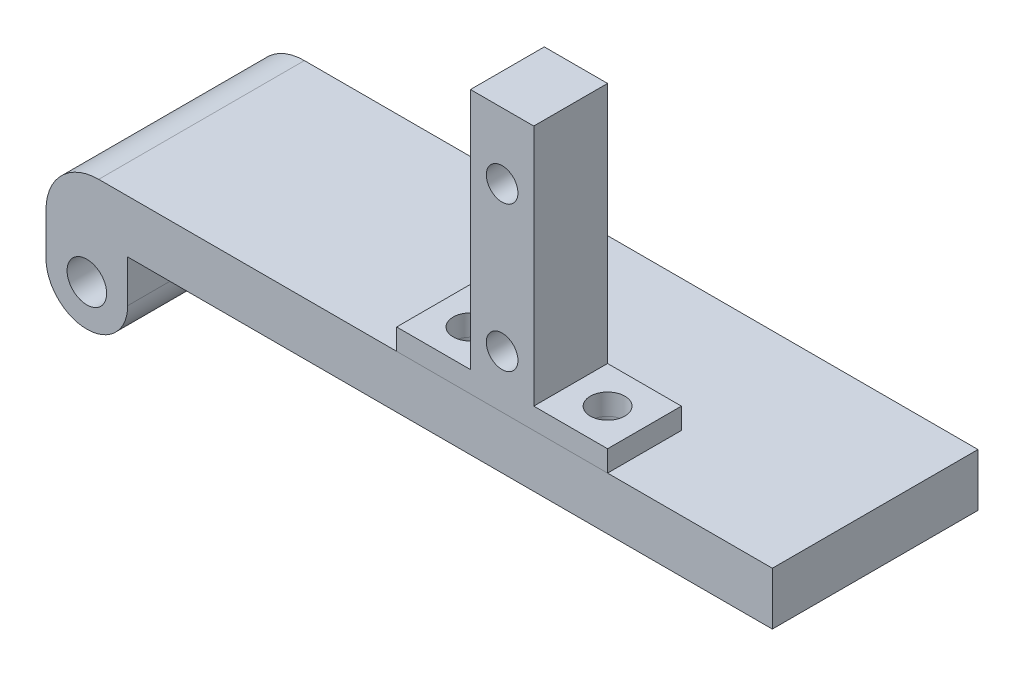
SolidWorks part; units mm, degrees
other "Motor Mount"
other "Lever Arm"
ref_plane "Front Plane" through (0, 0, 0) normal (0, 0, 1) x (1, 0, 0)
ref_plane "Top Plane" through (0, 0, 0) normal (0, 1, 0) x (1, 0, 0)
ref_plane "Right Plane" through (0, 0, 0) normal (1, 0, 0) x (0, 0, -1)
sketch "Sketch1" plane through (0, 0, 0) normal (0, 0, 1) x (1, 0, 0)
  line L0 (-37.3856, -8.255) -> (-37.3856, -3.175)
  line L1 (-37.3856, 3.175) -> (37.3856, 3.175)
  line L2 (-37.3856, 3.175) -> (-37.3856, -3.175)
  line L3 (-27.5431, -3.175) -> (37.3856, -3.175)
  line L4 (37.3856, 3.175) -> (37.3856, -3.175)
  line L5 (-37.3856, 3.175) -> (37.3856, -3.175) construction
  line L6 (-37.3856, -3.175) -> (37.3856, 3.175) construction
  line L7 (-27.5431, -8.255) -> (-27.5431, -3.175)
  circle A0 centre (-32.4644, -8.255) radius 2.3812
  arc A1 (-37.3856, -8.255) -> (-27.5431, -8.255) centre (-32.4644, -8.255) ccw
  point P0 (0, 0)
  dimension "D1" = 4.7625
  dimension "D3" = 2.54
  dimension "D2" = 6.35
  dimension "D4" = 69.85
  dimension "D5" = 5.08
extrude "Boss-Extrude1" add sketch "Sketch1" along normal blind 38.1
fillet "Fillet1" radius 6.35 1 edges at (-37.3856, 3.175, 19.05)
sketch "Sketch3" plane through (37.3856, 0, 0) normal (1, 0, 0) x (0, 0, -1)
  line L4 (0, -3.175) -> (0, 3.175)
  line L5 (0, 3.175) -> (-38.1, 3.175)
  line L6 (-38.1, 3.175) -> (-38.1, -3.175)
  line L7 (-38.1, -3.175) -> (0, -3.175)
  line L8 (0, -3.175) -> (0, 3.175)
  line L9 (0, 3.175) -> (-38.1, 3.175)
  line L10 (-38.1, 3.175) -> (-38.1, -3.175)
  line L11 (-38.1, -3.175) -> (0, -3.175)
  dimension "D1" = 0
extrude "Boss-Extrude2" add sketch "Sketch3" along normal blind 12.7
sketch "Sketch2" plane through (0, 3.175, 0) normal (0, 1, 0) x (1, 0, 0)
  line L1 (48.4981, -15.875) -> (11.9856, -15.875) construction
  line L2 (48.4981, -15.875) -> (48.4981, 0) construction
  line L3 (48.4981, 0) -> (11.9856, 0) construction
  line L4 (11.9856, -15.875) -> (11.9856, 0) construction
  line L5 (48.4981, -15.875) -> (11.9856, 0) construction
  line L6 (48.4981, 0) -> (11.9856, -15.875) construction
  line L7 (11.9856, -17.4625) -> (-16.5894, -17.4625) construction
  line L8 (11.9856, -17.4625) -> (11.9856, 1.5875) construction
  line L9 (11.9856, 1.5875) -> (-16.5894, 1.5875) construction
  line L10 (-16.5894, -17.4625) -> (-16.5894, 1.5875) construction
  line L11 (11.9856, -17.4625) -> (-16.5894, 1.5875) construction
  line L12 (11.9856, 1.5875) -> (-16.5894, -17.4625) construction
  line L13 (37.3856, -25.4) -> (37.3856, 9.525) construction
  line L14 (50.0856, 0) -> (-31.0356, 0) construction
  line L15 (-34.8456, -38.1) -> (-30.0831, -38.1) construction
  line L16 (-34.8456, -38.1) -> (-30.0831, -38.1) construction
  line L18 (21.3519, -24.765) -> (13.7319, -24.765)
  line L19 (21.3519, -24.765) -> (21.3519, -15.875)
  line L20 (21.3519, -15.875) -> (13.7319, -15.875)
  line L21 (13.7319, -24.765) -> (13.7319, -15.875)
  line L22 (21.3519, -24.765) -> (13.7319, -15.875) construction
  line L23 (21.3519, -15.875) -> (13.7319, -24.765) construction
  point P0 (30.2419, -7.9375)
  point P5 (17.5419, -20.32)
  point P6 (-2.3019, -7.9375)
  point P15 (17.5419, -20.32)
  point P21 (-32.4644, -38.1)
  point P26 (37.3856, -7.9375)
  dimension "Motor_Pos" = 15.875
  dimension "D2" = 36.5125
  dimension "D3" = 28.575
  dimension "D4" = 19.05
  dimension "D5" = 5.5562
  dimension "D6" = 11.1125
  dimension "D7" = 34.925
  dimension "D8" = 69.85
  dimension "D9" = 8.89
  dimension "D10" = 7.62
extrude "Boss-Extrude3" add sketch "Sketch2" along normal blind 31.75
sketch "Sketch5" plane through (0, 0, 24.765) normal (0, 0, 1) x (1, 0, 0)
  line L0 (17.5419, 34.925) -> (17.5419, 3.175) construction
  line L1 (13.7319, 34.925) -> (21.3519, 34.925) construction
  line L2 (13.7319, 3.175) -> (21.3519, 3.175) construction
  circle A0 centre (17.5419, 9.525) radius 1.905
  circle A1 centre (17.5419, 26.9875) radius 1.905
  dimension "D1" = 3.81
  dimension "D2" = 17.4625
  dimension "D3" = 6.35
extrude "Cut-Extrude1" cut sketch "Sketch5" against normal through all both and the other way through all
sketch "Sketch6" plane through (0, 3.175, 0) normal (0, 1, 0) x (1, 0, 0)
  line L0 (13.7319, -24.765) -> (21.3519, -24.765) construction
  line L1 (30.2419, -24.765) -> (4.8419, -24.765)
  line L2 (30.2419, -24.765) -> (30.2419, -15.875)
  line L3 (30.2419, -15.875) -> (4.8419, -15.875)
  line L4 (4.8419, -24.765) -> (4.8419, -15.875)
  line L5 (30.2419, -24.765) -> (4.8419, -15.875) construction
  line L6 (30.2419, -15.875) -> (4.8419, -24.765) construction
  line L7 (21.3519, -15.875) -> (13.7319, -15.875) construction
  line L8 (15.6369, -24.765) -> (19.4469, -24.765) construction
  line L9 (15.6369, -24.765) -> (19.4469, -24.765) construction
  line L10 (13.7319, -15.875) -> (13.7319, -24.765) construction
  point P0 (17.5419, -20.32)
  point P14 (17.5419, -24.765)
  dimension "D1" = 25.4
  dimension "D2" = 8.89
  dimension "D3" = 8.89
extrude "Boss-Extrude4" add sketch "Sketch6" along normal blind 2.54
sketch "Sketch7" plane through (0, 5.715, 0) normal (0, 1, 0) x (1, 0, 0)
  line L0 (4.8419, -24.765) -> (30.2419, -24.765) construction
  line L1 (13.7319, -24.765) -> (4.8419, -24.765) construction
  line L2 (13.7319, -24.765) -> (13.7319, -15.875) construction
  line L3 (13.7319, -15.875) -> (4.8419, -15.875) construction
  line L4 (4.8419, -24.765) -> (4.8419, -15.875) construction
  line L5 (13.7319, -24.765) -> (4.8419, -15.875) construction
  line L6 (13.7319, -15.875) -> (4.8419, -24.765) construction
  line L7 (13.7319, -15.875) -> (13.7319, -24.765) construction
  line L8 (15.6369, -24.765) -> (19.4469, -24.765) construction
  line L9 (15.6369, -24.765) -> (19.4469, -24.765) construction
  line L10 (17.5419, -24.765) -> (17.5419, -15.875) construction
  line L11 (30.2419, -15.875) -> (4.8419, -15.875) construction
  circle A0 centre (9.2869, -20.32) radius 2.0828
  circle A2 centre (25.7969, -20.32) radius 2.0828
  point P14 (17.5419, -24.765)
  dimension "D1" = 4.1656
extrude "Cut-Extrude2" cut sketch "Sketch7" against normal through all both and the other way through all
ref_plane "Plane1" through (-27.5431, -3.175, 38.1) normal (1, 0, 0) x (0, 0, -1)
sketch "Sketch9" plane through (0, 0, 38.1) normal (0, 0, 1) x (1, 0, 0)
  line L0 (50.0856, 3.175) -> (50.0856, -3.175) construction
  line L1 (-27.5431, -3.175) -> (50.0856, -3.175) construction
  line L2 (-27.5431, -8.255) -> (-27.5431, -3.175) construction
  line L3 (-37.3856, -3.175) -> (-37.3856, -8.255) construction
  line L4 (50.0856, 3.175) -> (-31.0356, 3.175) construction
  line L5 (50.0856, 3.175) -> (50.0856, -3.175)
  line L6 (-27.5431, -3.175) -> (50.0856, -3.175)
  line L7 (-27.5431, -8.255) -> (-27.5431, -3.175)
  line L8 (-37.3856, -3.175) -> (-37.3856, -8.255)
  line L9 (50.0856, 3.175) -> (-31.0356, 3.175)
  arc A0 (-37.3856, -8.255) -> (-27.5431, -8.255) centre (-32.4644, -8.255) ccw construction
  arc A1 (-31.0356, 3.175) -> (-37.3856, -3.175) centre (-31.0356, -3.175) ccw construction
  arc A2 (-37.3856, -8.255) -> (-27.5431, -8.255) centre (-32.4644, -8.255) ccw
  arc A3 (-31.0356, 3.175) -> (-37.3856, -3.175) centre (-31.0356, -3.175) ccw
extrude "Cut-Extrude3" cut sketch "Sketch9" against normal up to surface (13.335 mm away) up to face at (15.6369, 9.525, 24.765)
split "Split1" bodies to split 111 resulting bodies 107 108 split by face at (13.5334, 3.175, 16.3513)
